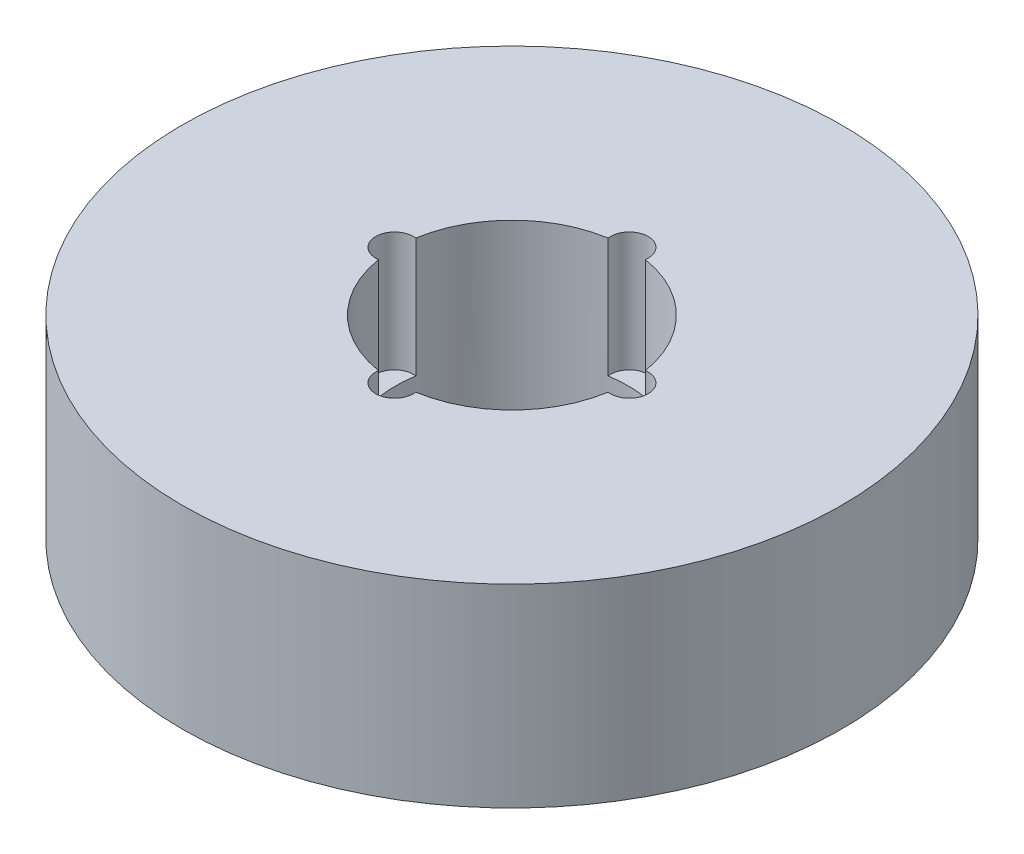
SolidWorks part; units mm, degrees
ref_plane "Front Plane" through (0, 0, 0) normal (0, 0, 1) x (1, 0, 0)
ref_plane "Top Plane" through (0, 0, 0) normal (0, 1, 0) x (1, 0, 0)
ref_plane "Right Plane" through (0, 0, 0) normal (1, 0, 0) x (0, 0, -1)
sketch "Sketch1" plane through (0, 0, 0) normal (0, 1, 0) x (1, 0, 0)
  circle A0 centre (0, 0) radius 42.5
  dimension "FLANGE_OD" = 85
extrude "Boss-Extrude1" add sketch "Sketch1" along normal blind 25
sketch "Sketch2" plane through (0, 0, 0) normal (0, 1, 0) x (1, 0, 0)
  circle A0 centre (0, 0) radius 15
  dimension "BORE_D" = 30
extrude "Cut-Extrude1" cut sketch "Sketch2" along normal through all
sketch "Sketch3" plane through (0, 25, 0) normal (0, 1, 0) x (1, 0, 0)
  circle A0 centre (0, 0) radius 15.1403 construction
  circle A1 centre (-15.1403, 0) radius 2.4269
  dimension "BOLT_D" = 4.8538
  dimension "BOLT_PCD" = 30.2806
extrude "Cut-Extrude2" cut sketch "Sketch3" against normal blind 15.3962
pattern_circular "CirPattern1" count 4 over 360 about axis through (0, 0, 0) along (0, 1, 0) of "Cut-Extrude2"
